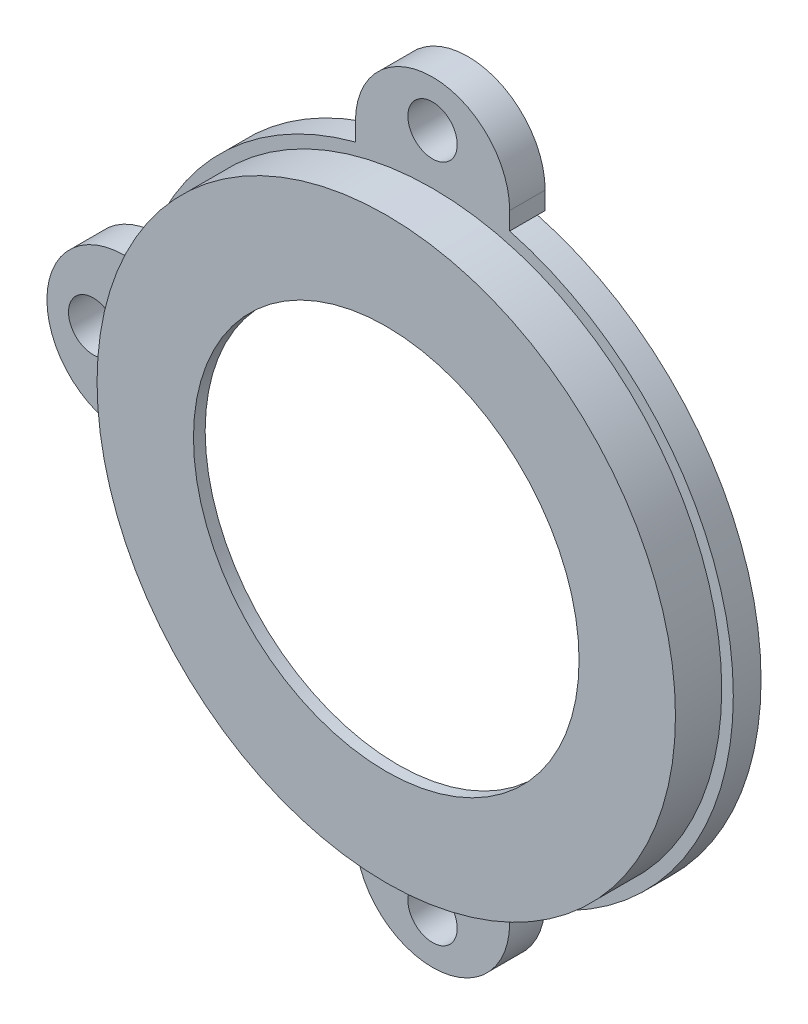
SolidWorks part; units mm, degrees
ref_plane "前视基准面" through (0, 0, 0) normal (0, 0, 1) x (1, 0, 0)
ref_plane "上视基准面" through (0, 0, 0) normal (0, 1, 0) x (1, 0, 0)
ref_plane "右视基准面" through (0, 0, 0) normal (1, 0, 0) x (0, 0, -1)
other "Configuration Table"
sketch "草图2" plane through (0, 0, 0) normal (0, 0, 1) x (1, 0, 0)
  line L0 (0, 0) -> (0, 22) construction
  line L1 (0, 0) -> (-22, 0) construction
  line L2 (5, 18.8481) -> (5, 25)
  line L3 (5, 25) -> (-5, 25)
  line L4 (-5, 25) -> (-5, 18.8481)
  line L5 (-18.8481, 5) -> (-25, 5)
  line L6 (-25, 5) -> (-25, -5)
  line L7 (-25, -5) -> (-18.8481, -5)
  line L8 (-5, -18.8481) -> (-5, -25)
  line L9 (-5, -25) -> (5, -25)
  line L10 (5, -25) -> (5, -18.8481)
  circle A0 centre (0, 0) radius 12.5
  circle A1 centre (0, 0) radius 19 construction
  circle A2 centre (0, 0) radius 22 construction
  circle A3 centre (0, 22) radius 1.6
  circle A4 centre (-22, 0) radius 1.6
  circle A5 centre (0, -22) radius 1.6
  arc A7 (5, -18.8481) -> (5, 18.8481) centre (0, 0) ccw
  arc A8 (-5, 18.8481) -> (-18.8481, 5) centre (0, 0) ccw
  arc A9 (-18.8481, -5) -> (-5, -18.8481) centre (0, 0) ccw
  dimension "D1" = 25
  dimension "D2" = 38
  dimension "D3" = 44
  dimension "D4" = 3.2
  dimension "D5" = 3
  dimension "D7" = 19.5
  dimension "D6" = 90
  dimension "D8" = 5
  dimension "D9" = 5
  dimension "D10" = 3
  dimension "D11" = 5
  dimension "D12" = 3
  dimension "D13" = 10
  dimension "D14" = 5
  dimension "D15" = 3
extrude "凸台-拉伸1" add sketch "草图2" along normal blind 1.8
fillet "圆角1" radius 5 6 edges at (5, -25, 0.9) (-5, -25, 0.9) (5, 25, 0.9) (-5, 25, 0.9) (-25, -5, 0.9) (-25, 5, 0.9)
sketch "草图7" plane through (0, 0, 1.8) normal (0, 0, 1) x (1, 0, 0)
  circle A0 centre (0, 0) radius 18.75
  circle A1 centre (0, 0) radius 12.5
  dimension "D1" = 37.5
  dimension "D2" = 25
extrude "凸台-拉伸2" add sketch "草图7" along normal blind 3
sketch "草图3" plane through (0, 0, 0) normal (0, 1, 0) x (1, 0, 0)
  line L0 (11.1862, -4.8) -> (19.5, 0)
  line L1 (11.1862, -4.8) -> (11.1862, 0)
  line L3 (11.1862, 0) -> (19.5, 0)
  line L5 (0, 0) -> (0, 4.4024) construction
  line L6 (-18.75, -4.8) -> (18.75, -4.8) construction
  dimension "D1" = 30
revolve "切除-旋转1" cut sketch "草图3" angle 360 about L5 region at (13.9574, 0, 1.6)
sketch "草图8" plane through (0, 0, 0) normal (0, 0, -1) x (-1, 0, 0)
  line L2 (-5, 20) -> (-5, 18.8481)
  line L3 (5, 18.8481) -> (5, 20)
  line L4 (-5, 20) -> (-5, 18.8481)
  line L5 (5, 18.8481) -> (5, 20)
  line L6 (20, 5) -> (18.8481, 5)
  line L7 (18.8481, -5) -> (20, -5)
  line L8 (20, 5) -> (18.8481, 5)
  line L9 (18.8481, -5) -> (20, -5)
  line L10 (5, -20) -> (5, -18.8481)
  line L11 (-5, -18.8481) -> (-5, -20)
  line L12 (5, -20) -> (5, -18.8481)
  line L13 (-5, -18.8481) -> (-5, -20)
  circle A0 centre (0, 22) radius 1.6 construction
  circle A1 centre (0, 22) radius 1.6
  circle A2 centre (22, 0) radius 1.6 construction
  arc A3 (5, 18.8481) -> (-5, 18.8481) centre (0, 0) ccw
  arc A4 (5, 20) -> (0, 25) centre (0, 20) ccw
  arc A5 (0, 25) -> (-5, 20) centre (0, 20) ccw
  arc A6 (5, 18.8481) -> (-5, 18.8481) centre (0, 0) ccw
  arc A7 (5, 20) -> (0, 25) centre (0, 20) ccw
  arc A8 (0, 25) -> (-5, 20) centre (0, 20) ccw
  arc A9 (18.8481, -5) -> (18.8481, 5) centre (0, 0) ccw
  arc A10 (20, -5) -> (25, 0) centre (20, 0) ccw
  arc A11 (25, 0) -> (20, 5) centre (20, 0) ccw
  arc A12 (18.8481, -5) -> (18.8481, 5) centre (0, 0) ccw
  arc A13 (20, -5) -> (25, 0) centre (20, 0) ccw
  arc A14 (25, 0) -> (20, 5) centre (20, 0) ccw
  arc A15 (-5, -18.8481) -> (5, -18.8481) centre (0, 0) ccw
  arc A16 (-5, -20) -> (0, -25) centre (0, -20) ccw
  arc A17 (0, -25) -> (5, -20) centre (0, -20) ccw
  arc A18 (-5, -18.8481) -> (5, -18.8481) centre (0, 0) ccw
  arc A19 (-5, -20) -> (0, -25) centre (0, -20) ccw
  arc A20 (0, -25) -> (5, -20) centre (0, -20) ccw
  circle A21 centre (22, 0) radius 1.6
  circle A22 centre (0, -22) radius 1.6 construction
  circle A23 centre (0, -22) radius 1.6
  dimension "D1" = 0
  dimension "D2" = 0
  dimension "D3" = 0
extrude "凸台-拉伸3" add sketch "草图8" along normal blind 0.5
